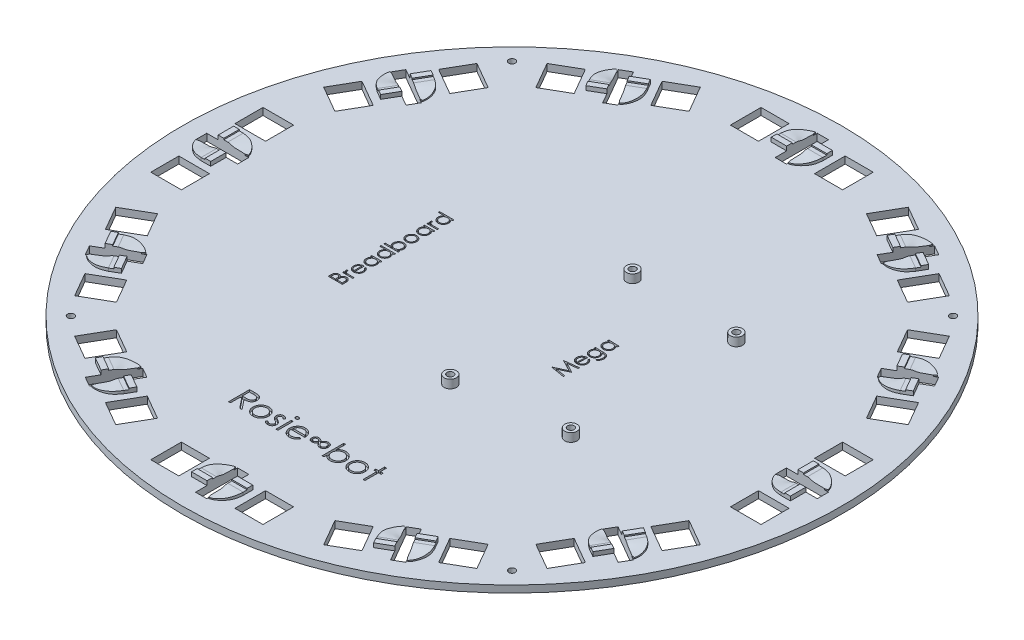
SolidWorks part; units mm, degrees
ref_plane "Front" through (0, 0, 0) normal (0, 0, 1) x (1, 0, 0)
ref_plane "Top" through (0, 0, 0) normal (0, 1, 0) x (1, 0, 0)
ref_plane "Right" through (0, 0, 0) normal (1, 0, 0) x (0, 0, -1)
sketch "Sketch1" plane through (0, 0, 0) normal (0, 1, 0) x (1, 0, 0)
  circle A0 centre (0, 0) radius 149.225
  dimension "D1" = 298.45
extrude "Base" add sketch "Sketch1" along normal blind 3.175 contours A0
sketch "Sketch2" plane through (0, 3.175, 0) normal (0, 1, 0) x (1, 0, 0)
  line L1 (-2.54, -140.758) -> (2.54, -140.758)
  line L2 (-2.54, -140.758) -> (-2.54, -121.708)
  line L3 (-2.54, -121.708) -> (2.54, -121.708)
  line L4 (2.54, -140.758) -> (2.54, -121.708)
  circle A0 centre (0, 0) radius 149.225 construction
  point P4 (0, -121.708)
  dimension "D1" = 5.08
  dimension "D2" = 19.05
  dimension "D3" = 140.758
extrude "Cut-Extrude1" cut sketch "Sketch2" against normal up to next and the other way through all contours L1 L4 L3 L2
sketch "Sketch4" plane through (0, 3.175, 0) normal (0, 1, 0) x (1, 0, 0)
  line L0 (0, -131.233) -> (-2.9434, -122.1742) construction
  line L1 (-2.9434, -122.1742) -> (0, -131.233) construction
  line L2 (0, -131.233) -> (-5.5987, -123.5271) construction
  line L3 (0, -131.233) -> (-7.7059, -125.6343) construction
  line L4 (0, -131.233) -> (-9.0588, -128.2896) construction
  line L5 (0, -131.233) -> (-9.525, -131.233) construction
  line L9 (2.54, -121.708) -> (-2.54, -121.708) construction
  line L10 (2.54, -121.708) -> (2.54, -140.758) construction
  line L11 (-2.54, -121.708) -> (-2.54, -140.758) construction
  line L12 (2.54, -140.758) -> (-2.54, -140.758) construction
  circle A0 centre (0, -131.233) radius 9.525 construction
  point P16 (0, -121.708)
  point P19 (2.54, -131.233)
  dimension "D1" = 18
  dimension "D2" = 18
  dimension "D3" = 18
  dimension "D4" = 18
  dimension "D5" = 18
ref_plane "Plane1" through (-38.5684, 0, 12.5316) normal (0.9511, 0, -0.309) x (-0.309, 0, -0.9511)
ref_plane "Plane2" through (-62.405, 0, 45.3399) normal (0.809, 0, -0.5878) x (-0.5878, 0, -0.809)
ref_plane "Plane3" through (-62.405, 0, 85.8931) normal (0.5878, 0, -0.809) x (-0.809, 0, -0.5878)
ref_plane "Plane4" through (-38.5684, 0, 118.7014) normal (0.309, 0, -0.9511) x (-0.9511, 0, -0.309)
ref_plane "Plane5" through (0, 0, 131.233) normal (0, 0, -1) x (-1, 0, 0)
sketch "Sketch5" plane through (-38.5684, 0, 12.5316) normal (0.9511, 0, -0.309) x (-0.309, 0, -0.9511)
  line L0 (-114.9663, 3.175) -> (-133.0839, 3.175) construction
  line L1 (-116.5904, 3.175) -> (-115.285, 3.175)
  line L2 (-116.5904, 3.175) -> (-116.5904, 3.683)
  line L3 (-116.5904, 3.683) -> (-115.285, 3.683)
  line L4 (-115.285, 3.175) -> (-115.285, 3.683)
  dimension "D2" = 0.508
sketch "Sketch6" plane through (-62.405, 0, 45.3399) normal (0.809, 0, -0.5878) x (-0.5878, 0, -0.809)
  line L0 (-96.9709, 3.175) -> (-112.3826, 3.175) construction
  line L1 (-101.8484, 3.175) -> (-96.6447, 3.175)
  line L2 (-101.8484, 3.175) -> (-101.8484, 3.775)
  line L3 (-101.8484, 3.775) -> (-96.6447, 3.775)
  line L4 (-96.6447, 3.175) -> (-96.6447, 3.775)
  dimension "D2" = 0.6
sketch "Sketch7" plane through (-62.405, 0, 85.8931) normal (0.5878, 0, -0.809) x (-0.809, 0, -0.5878)
  line L0 (-69.4833, 3.175) -> (-80.6806, 3.175) construction
  line L1 (-73.9972, 3.175) -> (-67.6118, 3.175)
  line L2 (-73.9972, 3.175) -> (-73.9972, 4.075)
  line L3 (-73.9972, 4.075) -> (-67.6118, 4.075)
  line L4 (-67.6118, 3.175) -> (-67.6118, 4.075)
  dimension "D2" = 0.9
sketch "Sketch10" plane through (-38.5684, 0, 118.7014) normal (0.309, 0, -0.9511) x (-0.9511, 0, -0.309)
  line L0 (-40.5532, 3.175) -> (-31.4944, 3.175) construction
  line L1 (-37.8825, 3.175) -> (-31.0282, 3.175)
  line L2 (-37.8825, 3.175) -> (-37.8825, 4.375)
  line L3 (-37.8825, 4.375) -> (-31.0282, 4.375)
  line L4 (-31.0282, 3.175) -> (-31.0282, 4.375)
  dimension "D3" = 1.2
sketch "Sketch11" plane through (0, 0, 131.233) normal (0, 0, -1) x (-1, 0, 0)
  line L0 (0, 3.175) -> (9.525, 3.175) construction
  line L1 (2.54, 3.175) -> (9.525, 3.175)
  line L2 (2.54, 3.175) -> (2.54, 4.475)
  line L3 (2.54, 4.475) -> (9.525, 4.475)
  line L4 (9.525, 3.175) -> (9.525, 4.475)
  dimension "D3" = 1.3
loft "Loft1" add profiles "Sketch5", "Sketch6", "Sketch7", "Sketch10", "Sketch11" connector at (-2.54, 3.683, 123.4157) connector at (-2.54, 3.775, 127.737) connector at (-2.54, 4.075, 129.3876) connector at (-2.54, 4.375, 130.4077) connector at (-2.54, 4.475, 131.233)
sketch "Sketch13" plane through (-104.9799, 0, 131.233) normal (0, 0, -1) x (-1, 0, 0)
  line L6 (-95.4549, 3.175) -> (-102.4399, 3.175)
  line L7 (-95.4549, 3.175) -> (-95.4549, 4.475)
  line L8 (-95.4549, 4.475) -> (-102.4399, 4.475)
  line L9 (-102.4399, 3.175) -> (-102.4399, 4.475)
extrude "Boss-Extrude4" add sketch "Sketch13" against normal blind 1.7907
sketch "Sketch25" plane through (0, 0, 133.0237) normal (0, 0, 1) x (1, 0, 0)
  line L0 (-9.525, 4.475) -> (-2.54, 4.475) construction
  line L1 (-9.525, 3.175) -> (-2.54, 3.175)
  line L2 (-9.525, 3.175) -> (-9.525, 5.075)
  line L3 (-9.525, 5.075) -> (-2.54, 5.075)
  line L4 (-2.54, 3.175) -> (-2.54, 5.075)
  dimension "D1" = 0.6
extrude "Boss-Extrude5" add sketch "Sketch25" along normal blind 2.54
sketch "Sketch14" plane through (-2.54, 0, 0) normal (1, 0, 0) x (0, 0, -1)
  line L0 (-131.233, 3.175) -> (-131.233, 0) construction
  line L1 (-121.708, 0) -> (-140.758, 0) construction
ref_plane "Plane6" through (0, 0, 0) normal (1, 0, 0) x (0, 0, -1)
sketch "Sketch15" plane through (0, 0, 0) normal (1, 0, 0) x (0, 0, -1)
  line L0 (-131.233, 0) -> (-131.233, 3.175) construction
pattern_circular "CirPattern1" count 2 over 360 about axis through (0, 0, 131.233) along (0, 1, 0) of "Loft1", "Boss-Extrude5", "Boss-Extrude4" reverse direction yes
ref_axis "Axis1" through (0, 50, 0) along (0, -1, 0)
pattern_circular "Full_Spiral_Pattern" count 12 over 360 about axis through (0, 50, 0) along (0, -1, 0) of "CirPattern1", "Cut-Extrude1"
sketch "Sketch18" plane through (0, 3.175, 0) normal (0, 1, 0) x (1, 0, 0)
  line L0 (12.7, 40.64) -> (60.96, 40.64) construction
  line L1 (12.7, 40.64) -> (12.7, -40.64) construction
  line L2 (60.96, -34.29) -> (12.7, -34.29) construction
  line L3 (60.96, -34.29) -> (60.96, 40.64) construction
  line L4 (0, -149.225) -> (0, 149.225) construction
  line L5 (0, -1.7463) -> (0, 1.7463) construction
  line L6 (-149.225, 0) -> (149.225, 0) construction
  line L7 (12.7, 41.91) -> (12.7, 40.64) construction
  circle A0 centre (12.7, 41.91) radius 2.77
  circle A1 centre (12.7, -40.64) radius 2.77
  circle A2 centre (60.96, -34.29) radius 2.77
  circle A3 centre (60.96, 40.64) radius 2.77
  circle A4 centre (12.7, -40.64) radius 1.5
  circle A5 centre (12.7, 41.91) radius 1.5
  circle A6 centre (60.96, 40.64) radius 1.5
  circle A7 centre (60.96, -34.29) radius 1.5
  circle A8 centre (0, 0) radius 149.225 construction
  point P22 (12.7, 0)
  dimension "D7" = 12.7
  dimension "D5" = 3
  dimension "D6" = 1.27
  dimension "D1" = 82.55
  dimension "D2" = 74.93
  dimension "D3" = 48.26
  dimension "D4" = 1.27
sketch "Sketch19" plane through (0, 3.175, 0) normal (0, 1, 0) x (1, 0, 0)
  line L0 (-99.8612, -99.8612) -> (0, 0) construction
  line L1 (0, -149.225) -> (0, 149.225) construction
  circle A1 centre (-99.8612, -99.8612) radius 1.5
  dimension "D4" = 3
  dimension "D5" = 45
  dimension "D1" = 141.225
extrude "Cut-Extrude2" cut sketch "Sketch19" against normal through all
pattern_circular "CirPattern7" count 4 over 360 about axis through (0, 50, 0) along (0, -1, 0) of "Cut-Extrude2"
extrude "MegaScrews" add sketch "Sketch18" along normal blind 3.81
sketch "Sketch23" plane through (0, 3.175, 0) normal (0, 1, 0) x (1, 0, 0)
  line L9 (-2.54, -135.5637) -> (-2.54, -140.758) construction
  line L10 (-25.4, -124.3051) -> (-12.7, -124.3051)
  line L11 (-25.4, -124.3051) -> (-25.4, -138.1608)
  line L16 (-25.4, -138.1608) -> (-12.7, -138.1608)
  line L17 (-12.7, -124.3051) -> (-12.7, -138.1608)
  line L19 (2.54, -121.708) -> (2.54, -126.9023) construction
  line L20 (0, -50) -> (0, 50) construction
  line L21 (12.7, -124.3051) -> (12.7, -138.1608)
  line L22 (25.4, -138.1608) -> (12.7, -138.1608)
  line L23 (25.4, -124.3051) -> (25.4, -138.1608)
  line L24 (25.4, -124.3051) -> (12.7, -124.3051)
  point P8 (-2.54, -138.1608)
  point P9 (2.54, -124.3051)
  dimension "D1" = 12.7
  dimension "D2" = 10.16
extrude "Cut-Extrude6" cut sketch "Sketch23" against normal through all
pattern_circular "CirPattern8" count 12 over 360 about axis through (0, 50, 0) along (0, -1, 0) of "Cut-Extrude6"
sketch "Sketch17" plane through (0, 3.175, 0) normal (0, 1, 0) x (1, 0, 0)
  line L0 (-31.75, -97.8162) -> (31.75, -97.8162) construction
  point P3 (0, -97.8162)
  dimension "D2" = 97.8162
  dimension "D1" = 63.5
sketch "Sketch16" plane through (0, 3.175, 0) normal (0, 1, 0) x (1, 0, 0)
  line L0 (-31.75, -97.8162) -> (31.75, -97.8162) construction
  text T0 "Rosie∞bot\r\n" font "Century Gothic" height in points 36
extrude "Cut-Extrude4" cut sketch "Sketch16" against normal blind 1.27
sketch "Sketch22" plane through (0, 3.175, 0) normal (0, 1, 0) x (1, 0, 0)
  line L0 (-50.8, 25.1735) -> (-50.8, -31.2294) construction
  text T0 "Breadboard"
  dimension "D1" = 50.8
extrude "Cut-Extrude5" cut sketch "Sketch22" against normal blind 1.27
sketch "Sketch24" plane through (0, 3.175, 0) normal (0, 1, 0) x (1, 0, 0)
  line L0 (35.4114, -12.631) -> (36.0762, 12.631) construction
  circle A0 centre (12.7, 41.91) radius 1.5 construction
  circle A1 centre (60.96, 40.64) radius 1.5 construction
  text T0 "Mega"
  point P12 (35.7438, 0)
extrude "Cut-Extrude7" cut sketch "Sketch24" against normal blind 1.27
equation "\"Diameter_Daisy\"= 11.75in'Outside diameter of base"
equation "\"D1@Sketch1\"=\"Diameter_Daisy\""
equation "\"D3@Sketch2\"=\"Diameter_Daisy\"/2-8.467mm"
equation "\"D1@Sketch19\"=\"Diameter_Daisy\"/2-8mm"
equation "\"Number_of_Holes\" = 12"
equation "\"D5@Sketch19\"=360/\"Number_of_Holes\"/2*3"
equation "\"D1@Full_Spiral_Pattern\"=\"Number_of_Holes\""
equation "\"D1@CirPattern8\"=\"Number_of_Holes\""
